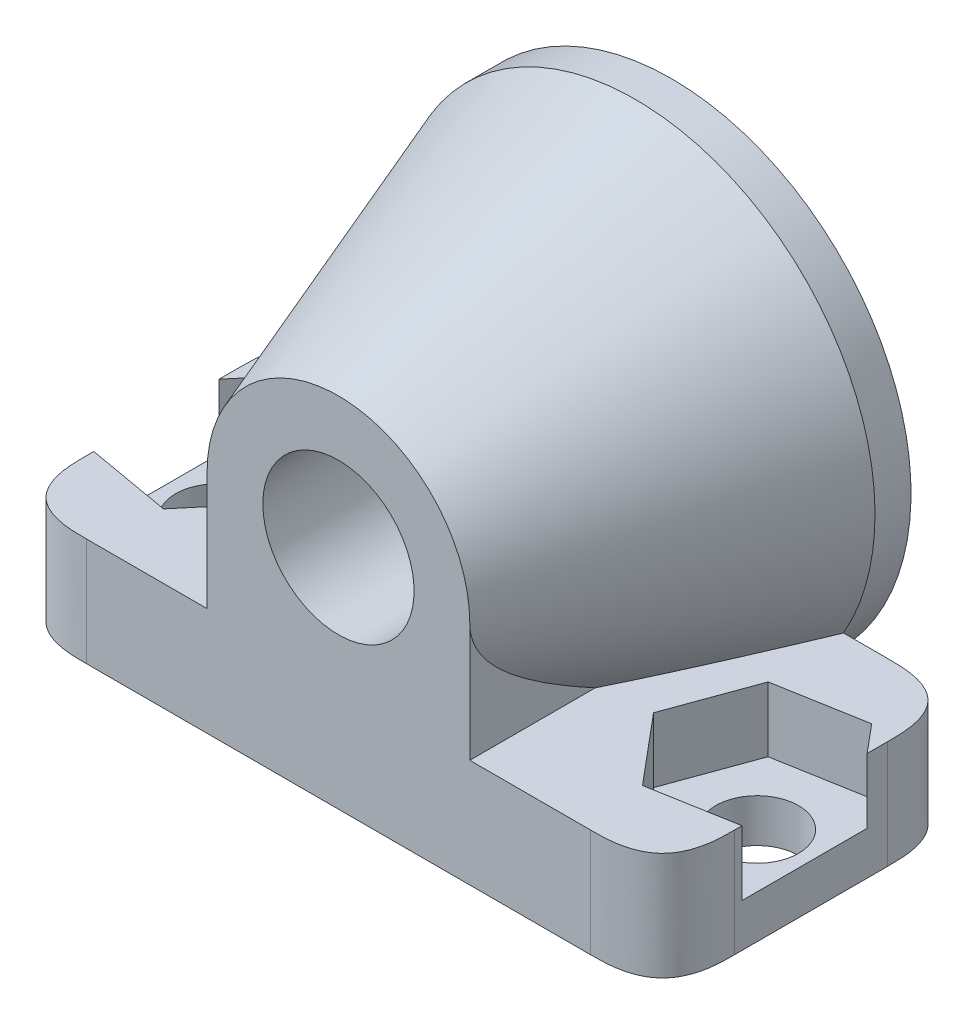
SolidWorks part; units mm, degrees
material "Nylon 101"
ref_plane "Front" through (0, 0, 0) normal (0, 0, 1) x (1, 0, 0)
ref_plane "Top" through (0, 0, 0) normal (0, 1, 0) x (1, 0, 0)
ref_plane "Right" through (0, 0, 0) normal (1, 0, 0) x (0, 0, -1)
ref_axis "X" through (-80.9, 0, 0) along (1, 0, 0)
ref_axis "Y" through (0, -10.2647, 0) along (0, 1, 0)
ref_axis "Z" through (0, 0, -80.9) along (0, 0, 1)
sketch "Sketch1" plane through (0, 0, 0) normal (0, 0, 1) x (1, 0, 0)
  line L7 (0, 0) -> (0, -6.295) construction
  circle A0 centre (0, 0) radius 6.65
  dimension "D1" = 13.3
  dimension "D2" = 6.295
extrude "Boss-Extrude1" add sketch "Sketch1" along normal blind 8.25 draft 20
sketch "Sketch2" plane through (0, 0, 0) normal (0, 0, -1) x (-1, 0, 0)
  circle A0 centre (0, 0) radius 5.45
  circle A1 centre (0, 0) radius 6.65
  point P3 (2.0621, -6.3222)
  point P4 (2.1261, -6.301)
  dimension "D1" = 10.9
  dimension "D2" = 13.3
extrude "Boss-Extrude2" add sketch "Sketch2" along normal blind 1
sketch "Sketch3" plane through (0, 0, 0) normal (0, 0, -1) x (-1, 0, 0)
  circle A0 centre (0, 0) radius 2.1
  dimension "D1" = 4.2
extrude "Cut-Extrude1" cut sketch "Sketch3" against normal through all
sketch "Sketch4" plane through (0, 0, 0) normal (0, 0, 1) x (1, 0, 0)
  line L0 (7.5, -6.295) -> (-7.5, -6.295)
  line L1 (-7.5, -6.295) -> (-7.5, -11.295)
  line L2 (-7.5, -11.295) -> (7.5, -11.295)
  line L3 (7.5, -11.295) -> (7.5, -6.295)
  line L4 (0, 0) -> (0, -6.295) construction
  dimension "D1" = 6.295
  dimension "D2" = 5
  dimension "D3" = 15
extrude "Cut-Extrude2" cut sketch "Sketch4" against normal through all both and the other way through all
sketch "Sketch5" plane through (0, 0, 0) normal (0, 0, 1) x (1, 0, 0)
  line L0 (3.6472, 0) -> (3.6472, -3.295)
  line L1 (3.6472, -3.295) -> (9, -3.295)
  line L2 (9, -3.295) -> (9, -6.295)
  line L3 (9, -6.295) -> (-9, -6.295)
  line L4 (-9, -6.295) -> (-9, -3.295)
  line L5 (-9, -3.295) -> (-3.6472, -3.295)
  line L6 (-3.6472, -3.295) -> (-3.6472, 0)
  line L7 (0, 0) -> (0, -6.295) construction
  line L8 (2.1437, -6.295) -> (-2.1437, -6.295) construction
  arc A0 (3.6472, 0) -> (-3.6472, 0) centre (0, 0) ccw
  circle A1 centre (0, 0) radius 2.1
  circle A3 centre (0, 0) radius 2.1 construction
  circle A4 centre (0, 0) radius 3.6472 construction
  dimension "D1" = 3
  dimension "D3" = 18
extrude "Boss-Extrude3" add sketch "Sketch5" along normal up to surface (8.25 mm away) up to face at (-2.1, 0, 8.25)
sketch "Sketch6" plane through (0, -6.295, 0) normal (0, -1, 0) x (1, 0, 0)
  line L0 (-7.5, 4.125) -> (7.5, 4.125) construction
  line L1 (-6.6509, 6.4579) -> (-9.0958, 6.0268)
  line L2 (-9.0958, 6.0268) -> (-9.9449, 3.6939)
  line L3 (-9.9449, 3.6939) -> (-8.3491, 1.7921)
  line L4 (-8.3491, 1.7921) -> (-5.9042, 2.2232)
  line L5 (-5.9042, 2.2232) -> (-5.0551, 4.5561)
  line L6 (-5.0551, 4.5561) -> (-6.6509, 6.4579)
  line L7 (6.6509, 6.4579) -> (5.0551, 4.5561)
  line L8 (5.0551, 4.5561) -> (5.9042, 2.2232)
  line L9 (5.9042, 2.2232) -> (8.3491, 1.7921)
  line L10 (8.3491, 1.7921) -> (9.9449, 3.6939)
  line L11 (9.9449, 3.6939) -> (9.0958, 6.0268)
  line L12 (9.0958, 6.0268) -> (6.6509, 6.4579)
  line L13 (0, 0) -> (0, 4.125) construction
  line L14 (0, 4.125) -> (0, 8.25) construction
  line L15 (3.6472, 8.25) -> (-3.6472, 8.25) construction
  circle A0 centre (-7.5, 4.125) radius 2.15 construction
  circle A1 centre (7.5, 4.125) radius 2.15 construction
  point P22 (-9.446, 3.7003)
  point P23 (5.5738, 2.0929)
  dimension "D1" = 4.3
  dimension "D2" = 15
  dimension "D3" = 70
  dimension "D4" = 70
extrude "Cut-Extrude3" cut sketch "Sketch6" against normal up to next from offset 1.2 offset against normal yes
sketch "Sketch7" plane through (0, -6.295, 0) normal (0, -1, 0) x (1, 0, 0)
  circle A0 centre (7.5, 4.125) radius 1.15
  circle A1 centre (-7.5, 4.125) radius 1.15
  dimension "D1" = 2.3
extrude "Cut-Extrude4" cut sketch "Sketch7" against normal up to next
fillet "Fillet1" radius 2 4 edges at (9, -4.795, 0) (9, -4.795, 8.25) (-9, -4.795, 0) (-9, -4.795, 8.25) curvature continuous yes
